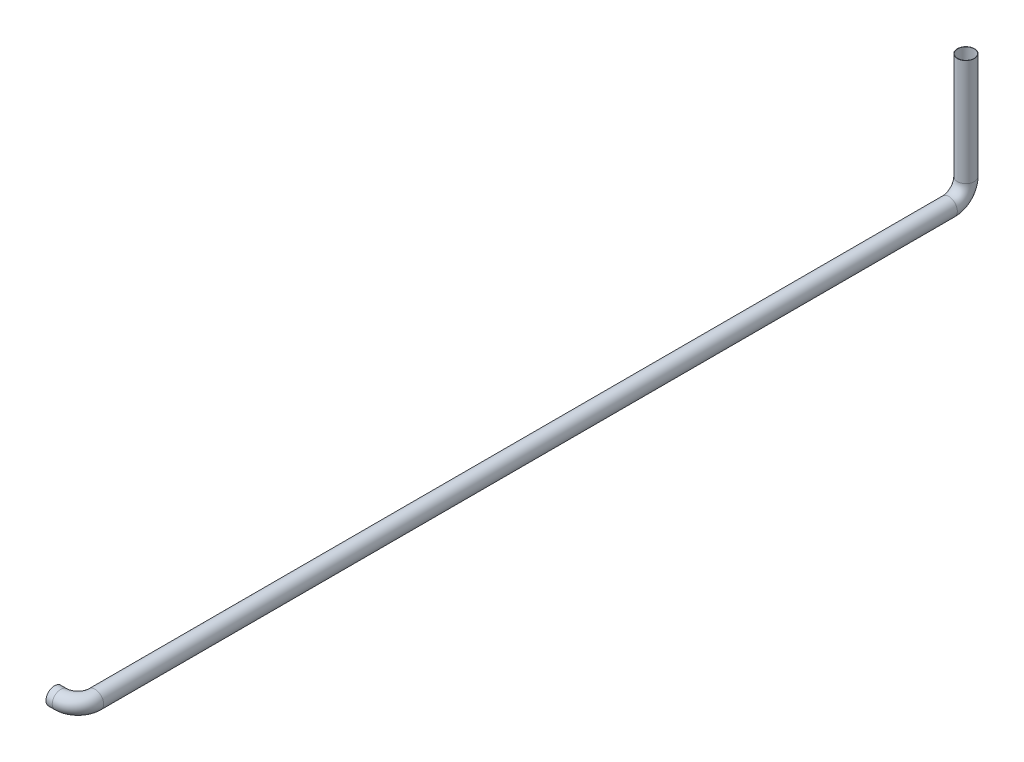
SolidWorks part; units mm, degrees
ref_plane "Plano frontal" through (0, 0, 0) normal (0, 0, 1) x (1, 0, 0)
ref_plane "Plano superior" through (0, 0, 0) normal (0, 1, 0) x (1, 0, 0)
ref_plane "Plano direito" through (0, 0, 0) normal (1, 0, 0) x (0, 0, -1)
sketch3d "3DSketch1"
  line L0 (-28941.6177, -14734.1334, 39013.8902) -> (-28941.6177, -14739.1334, 39013.8902) construction
  line L1 (-28941.6177, -14734.1334, 39013.8902) -> (-28941.6177, -12952.6734, 39013.8902) construction
  line L2 (-28941.6177, -14739.1334, 39013.8902) -> (-28941.6177, -15112.0136, 39013.8902)
  line L3 (-28941.6177, -15172.0136, 39073.8902) -> (-28941.6177, -15172.0136, 42061.7002)
  line L4 (-29001.6177, -15172.0136, 42121.7002) -> (-29023.422, -15172.0136, 42121.7002)
  line L5 (-29404.0326, -15172.0136, 42121.7002) -> (-29023.422, -15172.0136, 42121.7002) construction
  line L6 (-29932.2583, -15172.0136, 42121.7002) -> (-29264.2583, -15172.0136, 42121.7002) construction
  arc A1 (-28941.6177, -15172.0136, 39073.8902) -> (-28941.6177, -15112.0136, 39013.8902) centre (-28941.6177, -15112.0136, 39073.8902) ccw
  arc A2 (-28941.6177, -15172.0136, 42061.7002) -> (-29001.6177, -15172.0136, 42121.7002) centre (-29001.6177, -15172.0136, 42061.7002) ccw
  point P8 (-29032.6449, -15172.0136, 42121.7002)
  point P11 (0, 0, 0)
  point P12 (-29023.422, -15172.0136, 42121.7002)
  point P16 (-28941.6177, -15172.0136, 39013.8902)
  point P17 (-28881.6177, -15112.0136, 39073.8902)
  point P20 (-28941.6177, -15172.0136, 42121.7002)
  point P21 (-29001.6177, -15232.0136, 42061.7002)
  dimension "D1" = 60
sweep "Sweep-Thin1" add path "3DSketch1" circular profile diameter 60 parameters "D1"=1, "D3"=60
